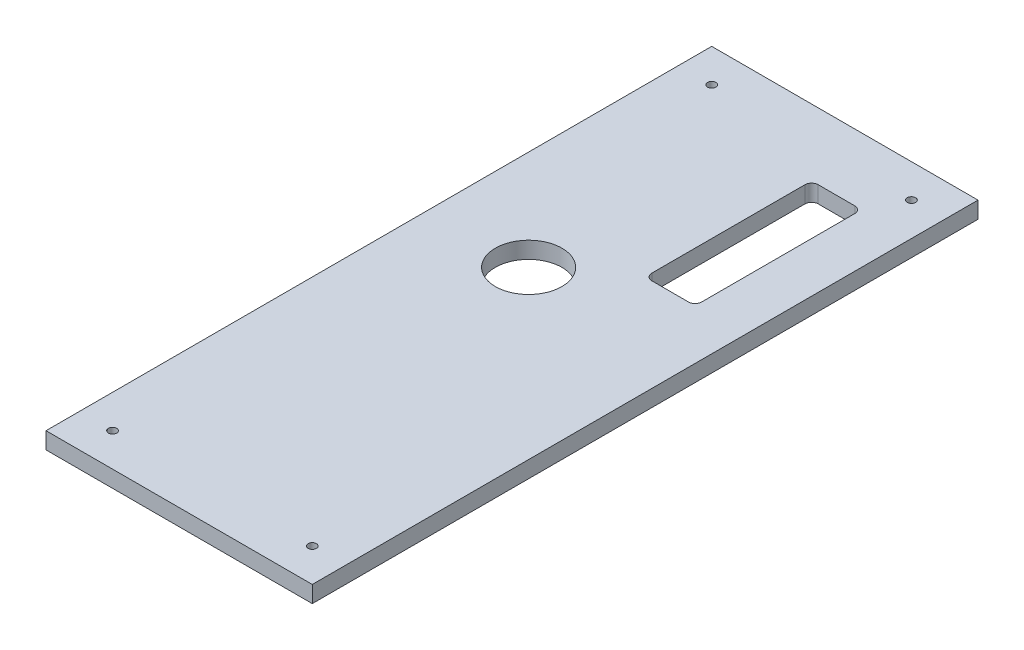
SolidWorks part; units mm, degrees
ref_plane "Front Plane" through (0, 0, 0) normal (0, 0, 1) x (1, 0, 0)
ref_plane "Top Plane" through (0, 0, 0) normal (0, 1, 0) x (1, 0, 0)
ref_plane "Right Plane" through (0, 0, 0) normal (1, 0, 0) x (0, 0, -1)
sketch "Sketch1" plane through (0, 0, 0) normal (0, 1, 0) x (1, 0, 0)
  line L0 (-50.8, 114.3) -> (50.8, 114.3) construction
  line L1 (50.8, -127) -> (-50.8, -127)
  line L2 (50.8, -127) -> (50.8, 127)
  line L3 (50.8, 127) -> (-50.8, 127)
  line L4 (-50.8, -127) -> (-50.8, 127)
  line L5 (50.8, -127) -> (-50.8, 127) construction
  line L6 (50.8, 127) -> (-50.8, -127) construction
  line L7 (29.21, 101.6) -> (15.24, 101.6)
  line L8 (31.75, 99.06) -> (31.75, 40.64)
  line L9 (29.21, 38.1) -> (15.24, 38.1)
  line L10 (12.7, 99.06) -> (12.7, 40.64)
  line L11 (-38.1, 127) -> (-38.1, -127) construction
  line L12 (-50.8, -114.3) -> (50.8, -114.3) construction
  line L13 (38.1, -127) -> (38.1, 127) construction
  circle A0 centre (-12.7, 19.05) radius 12.7
  arc A1 (15.24, 38.1) -> (12.7, 40.64) centre (15.24, 40.64) cw
  arc A2 (31.75, 40.64) -> (29.21, 38.1) centre (29.21, 40.64) cw
  arc A3 (29.21, 101.6) -> (31.75, 99.06) centre (29.21, 99.06) cw
  arc A4 (15.24, 101.6) -> (12.7, 99.06) centre (15.24, 99.06) ccw
  circle A5 centre (-38.1, -114.3) radius 1.5875
  circle A6 centre (38.1, -114.3) radius 1.5875
  circle A7 centre (38.1, 114.3) radius 1.5875
  circle A8 centre (-38.1, 114.3) radius 1.5875
  point P0 (0, 0)
  point P12 (-25.4, 19.05)
  point P13 (-12.7, 31.75)
  point P16 (12.7, 38.1)
  point P19 (31.75, 38.1)
  point P22 (31.75, 101.6)
  point P33 (-38.1, 114.3)
  point P35 (-38.1, -114.3)
  point P36 (38.1, -114.3)
  point P37 (38.1, 114.3)
  dimension "D2" = 25.4
  dimension "D10" = 2.54
  dimension "D11" = 3.175
  dimension "D1" = 101.6
  dimension "D3" = 19.05
  dimension "D4" = 19.05
  dimension "D5" = 63.5
  dimension "D6" = 25.4
  dimension "D7" = 95.25
  dimension "D8" = 25.4
  dimension "D9" = 254
  dimension "D12" = 12.7
  dimension "D13" = 12.7
  dimension "D14" = 12.7
  dimension "D15" = 12.7
extrude "Boss-Extrude1" add sketch "Sketch1" along normal blind 6.35
